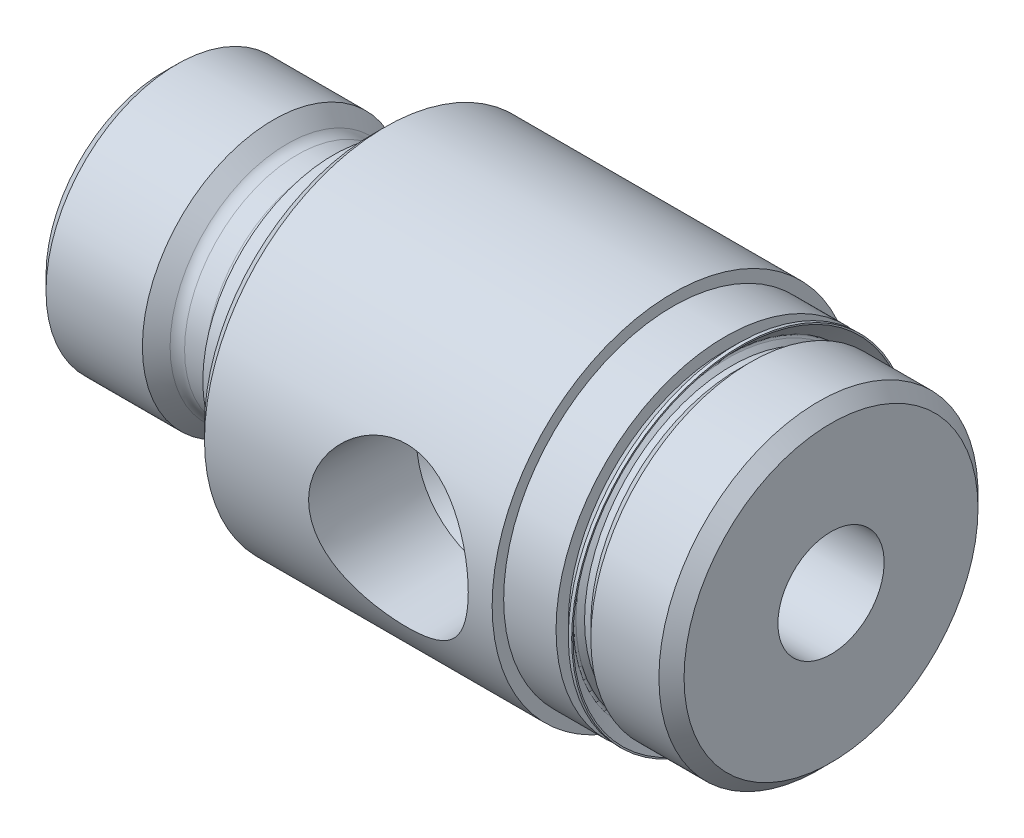
SolidWorks part; units mm, degrees
material "AISI 304"
ref_plane "Front Plane" through (0, 0, 0) normal (0, 0, 1) x (1, 0, 0)
ref_plane "Top Plane" through (0, 0, 0) normal (0, 1, 0) x (1, 0, 0)
ref_plane "Right Plane" through (0, 0, 0) normal (1, 0, 0) x (0, 0, -1)
sketch "Sketch1" plane through (0, 0, 0) normal (0, 0, 1) x (1, 0, 0)
  line L0 (0, 0) -> (0, 7.098)
  line L1 (0, 7.098) -> (0.8395, 7.9375)
  line L2 (0.8395, 7.9375) -> (6.6816, 7.9375)
  line L3 (6.6816, 7.9375) -> (7.5202, 7.0965)
  line L4 (8.1407, 6.8389) -> (9.4361, 6.8389)
  line L5 (10.3124, 7.7152) -> (10.3124, 7.9057)
  line L6 (10.3124, 7.9057) -> (12.7, 7.9057)
  line L7 (12.7, 7.9057) -> (12.7, 0)
  line L8 (12.7, 0) -> (0, 0)
  line L9 (12.7, 0) -> (0, 0) construction
  arc A0 (7.5202, 7.0965) -> (8.1407, 6.8389) centre (8.1407, 7.7152) ccw
  arc A1 (9.4361, 6.8389) -> (10.3124, 7.7152) centre (9.4361, 7.7152) ccw
revolve "Revolve1" add sketch "Sketch1" angle 360 about L9 reverse direction yes
cosmetic thread "Cosmetic Thread1" parameters "D1"=7.5202, "D2"=14.1961
sketch "Sketch2" plane through (0, 0, 0) normal (0, 0, 1) x (1, 0, 0)
  line L0 (12.7, 0) -> (12.7, 10.1918)
  line L1 (12.7, 10.1918) -> (13.462, 10.9537)
  line L2 (13.462, 10.9537) -> (34.0741, 10.9537)
  line L3 (34.0741, 10.9537) -> (34.0741, 8.9091)
  line L4 (34.0741, 8.9091) -> (34.8361, 8.9091)
  line L5 (34.8361, 8.9091) -> (35.5981, 9.671)
  line L6 (35.5981, 9.671) -> (39.7256, 9.671)
  line L7 (39.7256, 9.671) -> (40.4876, 8.9091)
  line L8 (40.4876, 8.9091) -> (40.4876, 0)
  line L9 (40.4876, 0) -> (12.7, 0)
  line L10 (40.4876, 0) -> (12.7, 0) construction
revolve "Revolve2" add sketch "Sketch2" angle 360 about L10 reverse direction yes
hole_wizard "Hole1" positions "Sketch4" profile "Sketch3" legacy
sketch "Sketch4" plane through (0, 0, 0) normal (-1, 0, 0) x (0, 0, 1)
  point P0 (0, 0)
sketch "Sketch3" plane through (0, 0, 0) normal (0, 1, 0) x (0, 0, 1)
  line L0 (0, 0) -> (0, 40.4876)
  line L1 (0, 40.4876) -> (3.2195, 40.4876)
  line L2 (3.2195, 40.4876) -> (3.2195, 0.254)
  line L3 (3.2195, 0.254) -> (3.4734, 0)
  line L4 (3.4734, 0) -> (0, 0)
  line L5 (0, -6.4453) -> (0, 115.525) construction
  line L6 (-3.2195, 0.254) -> (-3.4734, 0) construction
  dimension "Diameter" = 6.4389
  dimension "Depth" = 40.4876
  dimension "C-Sink Angle" = 90
  dimension "C-Sink Diameter" = 6.9469
sketch "Sketch5" plane through (0, 0, 0) normal (0, 0, 1) x (1, 0, 0)
  line L0 (30.8991, 10.2553) -> (34.0741, 10.2553)
  line L1 (34.0741, 10.2553) -> (34.0741, 15.3353)
  line L2 (34.0741, 15.3353) -> (30.8991, 15.3353)
  line L3 (30.8991, 15.3353) -> (30.8991, 10.2553)
  line L4 (34.0741, 0) -> (30.8991, 0) construction
revolve "Cut-Revolve1" cut sketch "Sketch5" angle 360 about L4 reverse direction yes
ref_plane "Plane1" through (11.9126, 0, 0) normal (1, 0, 0) x (0, 0, -1)
ref_plane "Plane2" through (11.9126, 0, 0) normal (1, 0, 0) x (0, 0, -1)
ref_plane "Plane3" through (0, 0, 0) normal (0, -0.7071, 0.7071) x (1, 0, 0)
ref_plane "Plane4" through (2.3368, 0, 0) normal (1, 0, 0) x (0, 0, -1)
ref_plane "Plane5" through (34.1376, 0, 0) normal (1, 0, 0) x (0, 0, -1)
ref_plane "Plane6" through (12.7, 0, 0) normal (1, 0, 0) x (0, 0, -1)
ref_plane "Plane7" through (34.1376, 0, 0) normal (1, 0, 0) x (0, 0, -1)
sketch "Sketch6" plane through (0, 0, 0) normal (0, 1, 0) x (1, 0, 0)
  line L0 (24.6126, 0) -> (27.7876, 0)
  line L1 (27.7876, 0) -> (27.7876, -3.1375)
  line L2 (27.7876, -3.1375) -> (29.2538, -4.6037)
  line L3 (29.2538, -4.6037) -> (29.4521, -10.9537)
  line L4 (29.4521, -10.9537) -> (24.6126, -10.9537)
  line L5 (24.6126, -10.9537) -> (24.6126, 0)
  line L6 (24.6126, -10.9537) -> (24.6126, 0) construction
revolve "Cut-Revolve2" cut sketch "Sketch6" angle 360 about L6 reverse direction yes
cosmetic thread "Cosmetic Thread2" parameters "D1"=3.81, "D2"=10.287
sketch "Sketch7" plane through (0, 0, 0) normal (0, 0, 1) x (1, 0, 0)
  line L0 (34.0741, 8.655) -> (34.8361, 8.655)
  line L1 (34.8361, 8.655) -> (34.8361, 8.9091)
  line L2 (34.8361, 8.9091) -> (34.4551, 8.9091)
  line L3 (34.4551, 8.9091) -> (34.1966, 9.1676)
  line L4 (34.1966, 9.3472) -> (35.0205, 10.1711)
  line L5 (35.0205, 10.1711) -> (35.0205, 10.2552)
  line L6 (35.0205, 10.2552) -> (34.8173, 10.2553)
  line L7 (34.8173, 10.2553) -> (34.0741, 9.512)
  line L8 (34.0741, 9.512) -> (34.0741, 8.655)
  line L9 (34.8361, 0) -> (34.0741, 0) construction
  arc A0 (34.1966, 9.1676) -> (34.1966, 9.3472) centre (34.2864, 9.2574) cw
revolve "Revolve3" add sketch "Sketch7" angle 360 about L9 reverse direction yes
ref_plane "Plane8" through (34.8361, 0, 0) normal (1, 0, 0) x (0, 0, -1)
ref_plane "Plane9" through (12.7, 0, 0) normal (1, 0, 0) x (0, 0, -1)
ref_plane "Plane10" through (10.3124, 0, 0) normal (1, 0, 0) x (0, 0, -1)
ref_plane "Plane11" through (0, 12.7, 0) normal (0, 1, 0) x (1, 0, 0)
ref_plane "Plane12" through (0, -12.7, 0) normal (0, 1, 0) x (1, 0, 0)
ref_plane "Plane13" through (12.7, 0, 0) normal (1, 0, 0) x (0, 0, -1)
ref_plane "Plane14" through (0, 0, 0) normal (0, 0, 1) x (1, 0, 0)
ref_plane "Plane15" through (0, 0, 0) normal (0, 1, 0) x (1, 0, 0)
ref_plane "Plane16" through (0, 0, 0) normal (0, 1, 0) x (1, 0, 0)
ref_plane "Plane17" through (0, 2.032, 0) normal (0, 1, 0) x (1, 0, 0)
ref_plane "Plane18" through (0, 0, 0) normal (1, 0, 0) x (0, 0, -1)
ref_plane "dp1 XY" through (0, 0, 0) normal (0, 0, 1) x (1, 0, 0)
ref_plane "dp1 XZ" through (0, 7.9057, 0) normal (0, -1, 0) x (-1, 0, 0)
ref_plane "dp1 YZ" through (12.7, 0, 0) normal (1, 0, 0) x (0, 0, -1)
ref_axis "dp1 X" through (-80.9, 7.9057, 0) along (1, 0, 0)
ref_axis "dp1 Y" through (12.7, -50, 0) along (0, 1, 0)
ref_axis "dp1 Z" through (12.7, 7.9057, 80.9) along (0, 0, -1)
sketch3d "dp1"
  point P0 (12.7, 7.9057, 0)
ref_plane "dp2 XY" through (0, 0, 0) normal (0, 0, 1) x (1, 0, 0)
ref_plane "dp2 XZ" through (0, -7.9057, 0) normal (0, -1, 0) x (-1, 0, 0)
ref_plane "dp2 YZ" through (12.7, 0, 0) normal (1, 0, 0) x (0, 0, -1)
ref_axis "dp2 X" through (-80.9, -7.9057, 0) along (1, 0, 0)
ref_axis "dp2 Y" through (12.7, -50, 0) along (0, 1, 0)
ref_axis "dp2 Z" through (12.7, -7.9057, 80.9) along (0, 0, -1)
sketch3d "dp2"
  point P0 (12.7, -7.9057, 0)
ref_plane "port XY" through (0, 0, 0) normal (0, 0, 1) x (1, 0, 0)
ref_plane "port XZ" through (0, 0, 0) normal (0, -1, 0) x (-1, 0, 0)
ref_plane "port YZ" through (24.6126, 0, 0) normal (1, 0, 0) x (0, 0, -1)
ref_axis "port X" through (-80.9, 0, 0) along (1, 0, 0)
ref_axis "port Y" through (24.6126, -50, 0) along (0, 1, 0)
ref_axis "port Z" through (24.6126, 0, 80.9) along (0, 0, -1)
sketch3d "port"
  point P0 (24.6126, 0, 0)
ref_plane "rod_guide XY" through (0, 0, 0) normal (1, 0, 0) x (0, 0, -1)
ref_plane "rod_guide XZ" through (0, 0, 0) normal (0, -1, 0) x (-1, 0, 0)
ref_plane "rod_guide YZ" through (0, 0, 0) normal (0, 0, -1) x (-1, 0, 0)
ref_axis "rod_guide X" through (0, 0, 80.9) along (0, 0, -1)
ref_axis "rod_guide Y" through (0, -50, 0) along (0, 1, 0)
ref_axis "rod_guide Z" through (80.9, 0, 0) along (-1, 0, 0)
sketch3d "rod_guide"
  point P0 (0, 0, 0)
ref_plane "s1 XY" through (0, 0, 0) normal (0, 0, 1) x (1, 0, 0)
ref_plane "s1 XZ" through (0, 0, 0) normal (0, -1, 0) x (-1, 0, 0)
ref_plane "s1 YZ" through (10.3124, 0, 0) normal (1, 0, 0) x (0, 0, -1)
ref_axis "s1 X" through (-80.9, 0, 0) along (1, 0, 0)
ref_axis "s1 Y" through (10.3124, -50, 0) along (0, 1, 0)
ref_axis "s1 Z" through (10.3124, 0, 80.9) along (0, 0, -1)
sketch3d "s1"
  point P0 (10.3124, 0, 0)
ref_plane "s2 XY" through (0, 0, 0) normal (0, 0, 1) x (1, 0, 0)
ref_plane "s2 XZ" through (0, 0, 0) normal (0, -1, 0) x (-1, 0, 0)
ref_plane "s2 YZ" through (12.7, 0, 0) normal (1, 0, 0) x (0, 0, -1)
ref_axis "s2 X" through (-80.9, 0, 0) along (1, 0, 0)
ref_axis "s2 Y" through (12.7, -50, 0) along (0, 1, 0)
ref_axis "s2 Z" through (12.7, 0, 80.9) along (0, 0, -1)
sketch3d "s2"
  point P0 (12.7, 0, 0)
ref_plane "t1 XY" through (12.7, 0, 0) normal (1, 0, 0) x (0, 0, -1)
ref_plane "t1 XZ" through (0, 0, 0) normal (0, -1, 0) x (-1, 0, 0)
ref_plane "t1 YZ" through (0, 0, 0) normal (0, 0, -1) x (-1, 0, 0)
ref_axis "t1 X" through (12.7, 0, 80.9) along (0, 0, -1)
ref_axis "t1 Y" through (12.7, -50, 0) along (0, 1, 0)
ref_axis "t1 Z" through (80.9, 0, 0) along (-1, 0, 0)
sketch3d "t1"
  point P0 (12.7, 0, 0)
ref_plane "t111 XY" through (12.7, 0, 0) normal (1, 0, 0) x (0, 0, -1)
ref_plane "t111 XZ" through (0, 0, 0) normal (0, -1, 0) x (-1, 0, 0)
ref_plane "t111 YZ" through (0, 0, 0) normal (0, 0, -1) x (-1, 0, 0)
ref_axis "t111 X" through (12.7, 0, 80.9) along (0, 0, -1)
ref_axis "t111 Y" through (12.7, -50, 0) along (0, 1, 0)
ref_axis "t111 Z" through (80.9, 0, 0) along (-1, 0, 0)
sketch3d "t111"
  point P0 (12.7, 0, 0)
ref_plane "to_foot_bracket XY" through (12.7, 0, 0) normal (1, 0, 0) x (0, 0, -1)
ref_plane "to_foot_bracket XZ" through (0, 0, 0) normal (0, -1, 0) x (-1, 0, 0)
ref_plane "to_foot_bracket YZ" through (0, 0, 0) normal (0, 0, -1) x (-1, 0, 0)
ref_axis "to_foot_bracket X" through (12.7, 0, 80.9) along (0, 0, -1)
ref_axis "to_foot_bracket Y" through (12.7, -50, 0) along (0, 1, 0)
ref_axis "to_foot_bracket Z" through (80.9, 0, 0) along (-1, 0, 0)
sketch3d "to_foot_bracket"
  point P0 (12.7, 0, 0)
ref_plane "to_nut XY" through (10.3124, 0, 0) normal (1, 0, 0) x (0, 0, -1)
ref_plane "to_nut XZ" through (0, 0, 0) normal (0, -1, 0) x (-1, 0, 0)
ref_plane "to_nut YZ" through (0, 0, 0) normal (0, 0, -1) x (-1, 0, 0)
ref_axis "to_nut X" through (10.3124, 0, 80.9) along (0, 0, -1)
ref_axis "to_nut Y" through (10.3124, -50, 0) along (0, 1, 0)
ref_axis "to_nut Z" through (80.9, 0, 0) along (-1, 0, 0)
sketch3d "to_nut"
  point P0 (10.3124, 0, 0)
ref_plane "to_rod XY" through (0, 0, 0) normal (1, 0, 0) x (0, 0, -1)
ref_plane "to_rod XZ" through (0, 0, 0) normal (0, -1, 0) x (-1, 0, 0)
ref_plane "to_rod YZ" through (0, 0, 0) normal (0, 0, -1) x (-1, 0, 0)
ref_axis "to_rod X" through (0, 0, 80.9) along (0, 0, -1)
ref_axis "to_rod Y" through (0, -50, 0) along (0, 1, 0)
ref_axis "to_rod Z" through (80.9, 0, 0) along (-1, 0, 0)
sketch3d "to_rod"
  point P0 (0, 0, 0)
ref_plane "to_screw XY" through (0, 2.032, 0) normal (0, 1, 0) x (1, 0, 0)
ref_plane "to_screw XZ" through (0, 0, -6.0452) normal (0, 0, 1) x (1, 0, 0)
ref_plane "to_screw YZ" through (24.6126, 0, 0) normal (1, 0, 0) x (0, 0, -1)
ref_axis "to_screw X" through (-80.9, 2.032, -6.0452) along (1, 0, 0)
ref_axis "to_screw Y" through (24.6126, 2.032, 50) along (0, 0, -1)
ref_axis "to_screw Z" through (24.6126, 50, -6.0452) along (0, -1, 0)
sketch3d "to_screw"
  point P0 (24.6126, 2.032, -6.0452)
ref_plane "to_trunnion_brackets XY" through (0, 0, 0) normal (0, 1, 0) x (1, 0, 0)
ref_plane "to_trunnion_brackets XZ" through (0, 0, 0) normal (0, 0, 1) x (1, 0, 0)
ref_plane "to_trunnion_brackets YZ" through (11.1252, 0, 0) normal (1, 0, 0) x (0, 0, -1)
ref_axis "to_trunnion_brackets X" through (-80.9, 0, 0) along (1, 0, 0)
ref_axis "to_trunnion_brackets Y" through (11.1252, 0, 50) along (0, 0, -1)
ref_axis "to_trunnion_brackets Z" through (11.1252, 50, 0) along (0, -1, 0)
sketch3d "to_trunnion_brackets"
  point P0 (11.1252, 0, 0)
ref_plane "to_trunnion_brackets1 XY" through (0, 12.7, 0) normal (0, 1, 0) x (1, 0, 0)
ref_plane "to_trunnion_brackets1 XZ" through (0, 0, 0) normal (0, 0, 1) x (1, 0, 0)
ref_plane "to_trunnion_brackets1 YZ" through (11.1252, 0, 0) normal (1, 0, 0) x (0, 0, -1)
ref_axis "to_trunnion_brackets1 X" through (-80.9, 12.7, 0) along (1, 0, 0)
ref_axis "to_trunnion_brackets1 Y" through (11.1252, 12.7, 50) along (0, 0, -1)
ref_axis "to_trunnion_brackets1 Z" through (11.1252, 50, 0) along (0, -1, 0)
sketch3d "to_trunnion_brackets1"
  point P0 (11.1252, 12.7, 0)
ref_plane "to_trunnion_brackets2 XY" through (0, -12.7, 0) normal (0, 1, 0) x (1, 0, 0)
ref_plane "to_trunnion_brackets2 XZ" through (0, 0, 0) normal (0, 0, 1) x (1, 0, 0)
ref_plane "to_trunnion_brackets2 YZ" through (11.1252, 0, 0) normal (1, 0, 0) x (0, 0, -1)
ref_axis "to_trunnion_brackets2 X" through (-80.9, -12.7, 0) along (1, 0, 0)
ref_axis "to_trunnion_brackets2 Y" through (11.1252, -12.7, 50) along (0, 0, -1)
ref_axis "to_trunnion_brackets2 Z" through (11.1252, 50, 0) along (0, -1, 0)
sketch3d "to_trunnion_brackets2"
  point P0 (11.1252, -12.7, 0)
ref_plane "to_tube XY" through (34.8361, 0, 0) normal (1, 0, 0) x (0, 0, -1)
ref_plane "to_tube XZ" through (0, 0, 0) normal (0, -1, 0) x (-1, 0, 0)
ref_plane "to_tube YZ" through (0, 0, 0) normal (0, 0, -1) x (-1, 0, 0)
ref_axis "to_tube X" through (34.8361, 0, 80.9) along (0, 0, -1)
ref_axis "to_tube Y" through (34.8361, -50, 0) along (0, 1, 0)
ref_axis "to_tube Z" through (80.9, 0, 0) along (-1, 0, 0)
sketch3d "to_tube"
  point P0 (34.8361, 0, 0)
